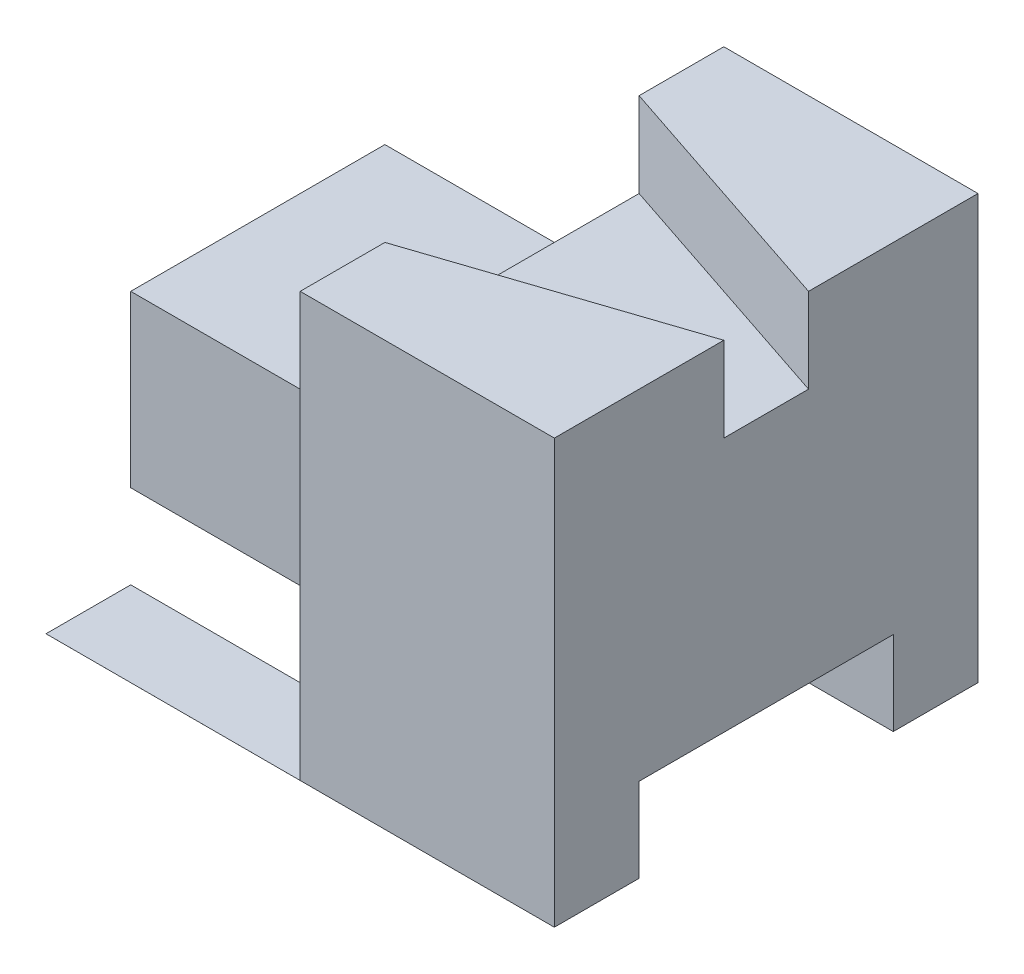
SolidWorks part; units mm, degrees
ref_plane "Front Plane" through (0, 0, 0) normal (0, 0, 1) x (1, 0, 0)
ref_plane "Top Plane" through (0, 0, 0) normal (0, 1, 0) x (1, 0, 0)
ref_plane "Right Plane" through (0, 0, 0) normal (1, 0, 0) x (0, 0, -1)
sketch "Sketch1" plane through (0, 0, 0) normal (0, 0, 1) x (1, 0, 0)
  line L1 (0, 0) -> (30, 0)
  line L2 (0, 0) -> (0, 50)
  line L3 (0, 50) -> (30, 50)
  line L4 (30, 0) -> (30, 50)
  dimension "D1" = 30
  dimension "D2" = 50
extrude "Boss-Extrude1" add sketch "Sketch1" along normal blind 50
sketch "Sketch2" plane through (0, 0, 50) normal (0, 0, 1) x (1, 0, 0)
  line L0 (0, 50) -> (0, 0) construction
  line L1 (0, 30) -> (-30, 30)
  line L2 (0, 30) -> (0, 10)
  line L3 (0, 10) -> (-30, 10)
  line L4 (-30, 30) -> (-30, 10)
  dimension "D1" = 30
  dimension "D2" = 20
  dimension "D3" = 10
extrude "Boss-Extrude2" add sketch "Sketch2" against normal blind 30
sketch "Sketch3" plane through (0, 0, 50) normal (0, 0, 1) x (1, 0, 0)
  line L1 (0, 10) -> (-30, 10)
  line L2 (0, 10) -> (0, 30)
  line L3 (0, 30) -> (-30, 30)
  line L4 (-30, 10) -> (-30, 30)
extrude "Cut-Extrude1" cut sketch "Sketch3" against normal blind 10
sketch "Sketch4" plane through (0, 0, 20) normal (0, 0, -1) x (-1, 0, 0)
  line L1 (0, 30) -> (30, 30)
  line L2 (0, 30) -> (0, 10)
  line L3 (0, 10) -> (30, 10)
  line L4 (30, 30) -> (30, 10)
extrude "Boss-Extrude3" add sketch "Sketch4" along normal blind 10
sketch "Sketch6" plane through (0, 50, 0) normal (0, 1, 0) x (1, 0, 0)
  line L1 (0, 0) -> (30, 0)
  line L2 (0, 0) -> (0, -50)
  line L3 (0, -50) -> (30, -50)
  line L4 (30, 0) -> (30, -50)
extrude "Cut-Extrude2" cut sketch "Sketch6" against normal blind 10
ref_plane "Plane1" through (0, 0, 40) normal (0, 0, 1) x (1, 0, 0)
ref_plane "Plane2" through (0, 0, 30) normal (0, 0, 1) x (1, 0, 0)
sketch "Sketch9" plane through (0, 0, 30) normal (0, 0, 1) x (1, 0, 0)
  line L0 (-30, 0) -> (0, 0)
  line L1 (-30, 0) -> (0, 40)
  line L2 (0, 40) -> (0, 0)
  dimension "D1" = 30
  dimension "D2" = 40
extrude "Boss-Extrude6" add sketch "Sketch9" against normal blind 30
sketch "Sketch10" plane through (0, 0, 50) normal (0, 0, 1) x (1, 0, 0)
  line L0 (0, 40) -> (30, 40) construction
  line L1 (30, 40) -> (0, 40)
  line L2 (30, 40) -> (30, 50)
  line L3 (30, 50) -> (0, 50)
  line L4 (0, 40) -> (0, 50)
  line L5 (30, 0) -> (30, 40) construction
  dimension "D1" = 30
  dimension "D2" = 10
extrude "Boss-Extrude8" add sketch "Sketch10" against normal blind 5
sketch "Sketch11" plane through (0, 0, 45) normal (0, 0, -1) x (-1, 0, 0)
  line L1 (-30, 50) -> (0, 50)
  line L2 (-30, 50) -> (-30, 40)
  line L3 (-30, 40) -> (0, 40)
  line L4 (0, 50) -> (0, 40)
extrude "Boss-Extrude9" add sketch "Sketch11" along normal blind 5
sketch "Sketch12" plane through (0, 40, 0) normal (0, 1, 0) x (1, 0, 0)
  line L0 (0, -40) -> (30, -30)
  line L1 (30, -40) -> (30, 0) construction
  line L2 (30, -30) -> (30, -40)
  line L3 (30, -40) -> (0, -40)
  dimension "D1" = 10
extrude "Boss-Extrude10" add sketch "Sketch12" along normal blind 10
sketch "Sketch13" plane through (0, 40, 0) normal (0, 1, 0) x (1, 0, 0)
  line L0 (0, 0) -> (30, 0)
  line L1 (30, 0) -> (30, -20)
  line L2 (30, -30) -> (30, 0) construction
  line L3 (30, -20) -> (0, -10)
  line L4 (0, 0) -> (0, -30) construction
  line L5 (0, -10) -> (0, 0)
  dimension "D1" = 20
  dimension "D2" = 10
extrude "Boss-Extrude11" add sketch "Sketch13" along normal blind 10
sketch "Sketch14" plane through (0, 0, 0) normal (1, 0, 0) x (0, 0, -1)
  line L0 (-50, 0) -> (-30, 0) construction
  line L1 (-40, 0) -> (-10, 0)
  line L2 (-40, 0) -> (-40, 10)
  line L3 (-40, 10) -> (-10, 10)
  line L4 (-10, 0) -> (-10, 10)
  dimension "D1" = 10
  dimension "D2" = 30
  dimension "D3" = 10
extrude "Cut-Extrude3" cut sketch "Sketch14" against normal blind 30 and the other way blind 30
sketch "Sketch15" plane through (0, 0, 30) normal (0, 0, 1) x (1, 0, 0)
  line L0 (-7.5, 30) -> (0, 30)
  line L1 (0, 30) -> (0, 40)
  line L2 (0, 40) -> (-7.5, 30)
extrude "Cut-Extrude4" cut sketch "Sketch15" against normal blind 20
sketch "Sketch19" plane through (0, 10, 0) normal (0, -1, 0) x (-1, 0, 0)
  line L1 (30, -40) -> (-6.8448, -40)
  line L2 (30, -40) -> (30, -25.8231)
  line L3 (30, -25.8231) -> (-6.8448, -25.8231)
  line L4 (-6.8448, -40) -> (-6.8448, -25.8231)
extrude "Boss-Extrude18" add sketch "Sketch19" along normal blind 10
sketch "Sketch20" plane through (0, 0, 50) normal (0, 0, 1) x (1, 0, 0)
  line L1 (0, 0) -> (-30, 0)
  line L2 (0, 0) -> (0, 10)
  line L3 (0, 10) -> (-30, 10)
  line L4 (-30, 0) -> (-30, 10)
  dimension "D1" = 30
  dimension "D2" = 10
extrude "Boss-Extrude19" add sketch "Sketch20" against normal blind 10
sketch "Sketch22" plane through (0, 0, 0) normal (0, -1, 0) x (-1, 0, 0)
  line L1 (-6.8448, -40) -> (30, -40)
  line L2 (-6.8448, -40) -> (-6.8448, -25.8231)
  line L3 (-6.8448, -25.8231) -> (30, -25.8231)
  line L4 (30, -40) -> (30, -25.8231)
extrude "Cut-Extrude6" cut sketch "Sketch22" against normal blind 9.75
sketch "Sketch25" plane through (0, 9.75, 0) normal (0, -1, 0) x (-1, 0, 0)
  line L1 (30, -25.8231) -> (-6.8448, -25.8231)
  line L2 (30, -25.8231) -> (30, -40)
  line L3 (30, -40) -> (-6.8448, -40)
  line L4 (-6.8448, -25.8231) -> (-6.8448, -40)
extrude "Cut-Extrude14" cut sketch "Sketch25" against normal blind 0.12
sketch "Sketch26" plane through (0, 9.87, 0) normal (0, -1, 0) x (1, 0, 0)
  line L1 (-30, 25.8231) -> (6.8448, 25.8231)
  line L2 (-30, 25.8231) -> (-30, 40)
  line L3 (-30, 40) -> (6.8448, 40)
  line L4 (6.8448, 25.8231) -> (6.8448, 40)
extrude "Cut-Extrude15" cut sketch "Sketch26" against normal blind 0.12
sketch "Sketch29" plane through (0, 10, 0) normal (0, -1, 0) x (1, 0, 0)
  line L1 (-30, 25.8231) -> (6.8448, 25.8231)
  line L2 (-30, 25.8231) -> (-30, 40)
  line L3 (-30, 40) -> (6.8448, 40)
  line L4 (6.8448, 25.8231) -> (6.8448, 40)
extrude "Boss-Extrude21" add sketch "Sketch29" along normal blind 0.05
sketch "Sketch31" plane through (0, 10, 0) normal (0, -1, 0) x (-1, 0, 0)
  line L1 (30, -10) -> (-30, -10)
  line L2 (30, -10) -> (30, -40)
  line L3 (30, -40) -> (-30, -40)
  line L4 (-30, -10) -> (-30, -40)
extrude "Boss-Extrude25" add sketch "Sketch31" along normal blind 0.08
sketch "Sketch32" plane through (0, 0, 50) normal (0, 0, 1) x (1, 0, 0)
  line L0 (-30, 0) -> (30, 0) construction
  line L1 (-30, 10) -> (0, 10)
  line L2 (-30, 10) -> (-30, 0)
  line L3 (-30, 0) -> (0, 0)
  line L4 (0, 10) -> (0, 0)
extrude "Cut-Extrude22" cut sketch "Sketch32" against normal blind 10
sketch "Sketch38" plane through (0, 0, 0) normal (-1, 0, 0) x (0, 0, 1)
  line L1 (50, 0) -> (40, 0)
  line L2 (50, 0) -> (50, 9.92)
  line L3 (50, 9.92) -> (40, 9.92)
  line L4 (40, 0) -> (40, 9.92)
extrude "Cut-Extrude26" cut sketch "Sketch38" against normal blind 0.001
sketch "Sketch39" plane through (0, 0, 0) normal (0, -1, 0) x (-1, 0, 0)
  line L1 (-0.001, -50) -> (29.999, -50)
  line L2 (-0.001, -50) -> (-0.001, -40)
  line L3 (-0.001, -40) -> (29.999, -40)
  line L4 (29.999, -50) -> (29.999, -40)
  dimension "D1" = 30
  dimension "D2" = 10
extrude "Boss-Extrude31" add sketch "Sketch39" against normal blind 0.001
